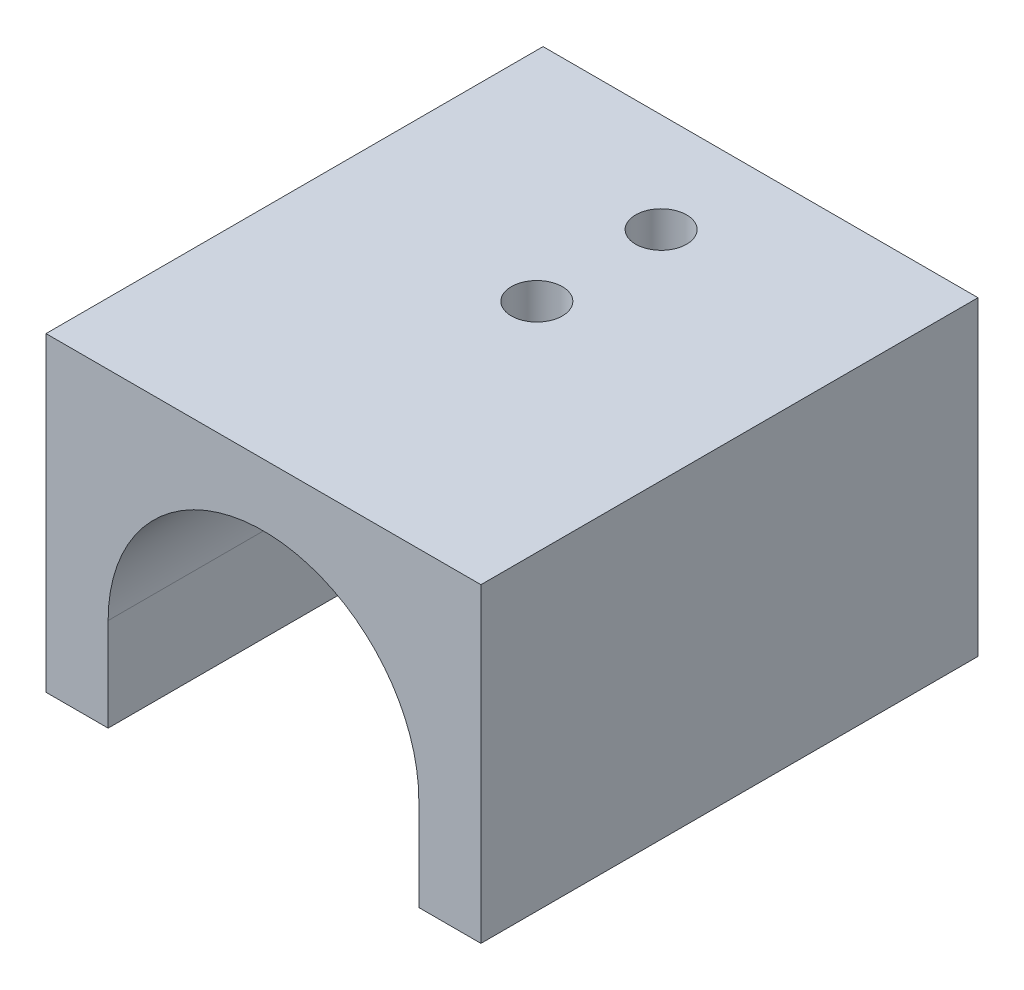
SolidWorks part; units mm, degrees
ref_plane "Front Plane" through (0, 0, 0) normal (0, 0, 1) x (1, 0, 0)
ref_plane "Top Plane" through (0, 0, 0) normal (0, 1, 0) x (1, 0, 0)
ref_plane "Right Plane" through (0, 0, 0) normal (1, 0, 0) x (0, 0, -1)
sketch "Sketch1" plane through (0, 0, 0) normal (0, 0, 1) x (1, 0, 0)
  line L0 (-17.5, 17.5) -> (17.5, 17.5)
  line L1 (-17.5, 17.5) -> (-17.5, -7.5)
  line L2 (17.5, 17.5) -> (17.5, -7.5)
  line L3 (12.5, -7.5) -> (12.5, 0)
  line L4 (17.5, -7.5) -> (12.5, -7.5)
  line L5 (-17.5, -7.5) -> (-12.5, -7.5)
  line L6 (-12.5, -7.5) -> (-12.5, 0)
  arc A0 (-12.5, 0) -> (12.5, 0) centre (0, 0) cw
  point P9 (0, 0)
  dimension "D1" = 12.5
  dimension "D2" = 5
  dimension "D3" = 17.5
  dimension "D4" = 25
extrude "Boss-Extrude1" add sketch "Sketch1" along normal mid plane 40
sketch "Sketch2" plane through (0, 17.5, 0) normal (0, 1, 0) x (1, 0, 0)
  line L0 (0, -44.7868) -> (0, 44.7868) construction
  line L1 (17.5, 20) -> (-17.5, 20) construction
  circle A0 centre (0, 12) radius 2.05
  circle A1 centre (0, 2) radius 2.05
  dimension "D3" = 4.1
  dimension "D1" = 10
  dimension "D2" = 8
extrude "Cut-Extrude1" cut sketch "Sketch2" against normal up to surface (5 mm away) up to face at (0, 6.25, 0)
equation "\"tubeRad\"=12.5"
equation "\"D1@Sketch1\"=\"tubeRad\""
equation "\"D3@Sketch1\"=\"tubeRad\"+5"
equation "\"D4@Sketch1\"=\"tubeRad\"*2"
equation "\"MountHoleSize\"=4.1"
equation "\"D3@Sketch2\"=\"MountHoleSize\""
